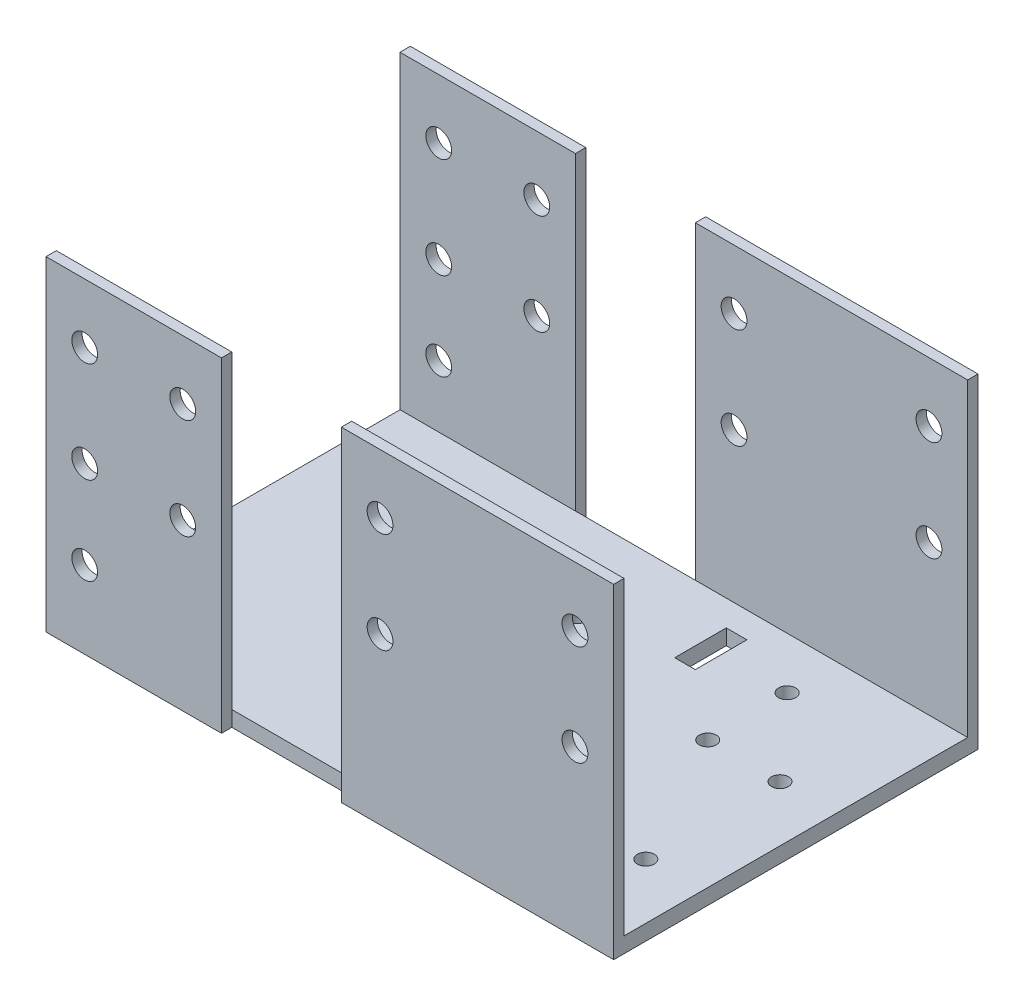
SolidWorks part; units mm, degrees
ref_plane "前视基准面" through (0, 0, 0) normal (0, 0, 1) x (1, 0, 0)
ref_plane "上视基准面" through (0, 0, 0) normal (0, 1, 0) x (1, 0, 0)
ref_plane "右视基准面" through (0, 0, 0) normal (1, 0, 0) x (0, 0, -1)
sketch "草图1" plane through (0, 0, 0) normal (0, 1, 0) x (1, 0, 0)
  line L1 (0, 0) -> (110, 0)
  line L2 (0, 0) -> (0, -66.6)
  line L3 (0, -66.6) -> (110, -66.6)
  line L4 (110, 0) -> (110, -66.6)
  line L5 (0, -66.6) -> (34, -66.6)
  line L6 (0, -66.6) -> (0, -68.6)
  line L7 (0, -68.6) -> (34, -68.6)
  line L8 (34, -66.6) -> (34, -68.6)
  line L9 (110, -66.6) -> (57.23, -66.6)
  line L10 (110, -66.6) -> (110, -68.6)
  line L11 (110, -68.6) -> (57.23, -68.6)
  line L12 (57.23, -66.6) -> (57.23, -68.6)
  line L13 (0, 0) -> (34, 0)
  line L14 (0, 0) -> (0, 2)
  line L15 (0, 2) -> (34, 2)
  line L16 (34, 0) -> (34, 2)
  line L17 (57.23, 0) -> (110, 0)
  line L18 (57.23, 0) -> (57.23, 2)
  line L19 (57.23, 2) -> (110, 2)
  line L20 (110, 0) -> (110, 2)
  line L21 (85.228, -59.5618) -> (99.228, -59.5618)
  line L22 (85.228, -59.5618) -> (85.228, -63.5618)
  line L23 (85.228, -63.5618) -> (99.228, -63.5618)
  line L24 (99.228, -59.5618) -> (99.228, -63.5618)
  line L25 (68.2195, -15) -> (72.2195, -15)
  line L26 (68.2195, -15) -> (68.2195, -5)
  line L27 (68.2195, -5) -> (72.2195, -5)
  line L28 (72.2195, -15) -> (72.2195, -5)
  line L29 (68.2195, -15) -> (72.2195, -5) construction
  line L30 (68.2195, -5) -> (72.2195, -15) construction
  circle A1 centre (99.228, -25.6) radius 1.65
  circle A2 centre (85.228, -25.6) radius 1.65
  circle A3 centre (85.228, -51.6) radius 1.65
  circle A4 centre (99.228, -51.6) radius 1.65
  circle A5 centre (85, -10) radius 1.65
  circle A6 centre (9.8926, -17.5518) radius 1.65
  circle A7 centre (51.8926, -17.5623) radius 1.65
  circle A8 centre (53.3861, -59.5623) radius 1.65
  circle A9 centre (11.3861, -59.5518) radius 1.65
  point P31 (70.2195, -10)
  point P44 (11.2794, -51.6)
  point P45 (41.2556, -56.573)
  point P46 (23.8673, -56.5746)
  point P47 (9.8926, -58.4932)
  point P48 (51.4966, -59.5618)
  point P49 (0, 0)
  point P50 (11.3861, -59.5623)
  dimension "D8" = 3.3
  dimension "D9" = 3.3
  dimension "D10" = 3.3
  dimension "D11" = 3.3
  dimension "D12" = 14
  dimension "D13" = 26
  dimension "D14" = 14
  dimension "D15" = 15
  dimension "D17" = 3.3
  dimension "D18" = 10
  dimension "D19" = 25
  dimension "D23" = 42
  dimension "D24" = 42
  dimension "D25" = 42
  dimension "D26" = 42
  dimension "D27" = 3.3
  dimension "D28" = 3.3
  dimension "D29" = 3.3
  dimension "D30" = 3.3
  dimension "D1" = 110
  dimension "D2" = 66.6
  dimension "D3" = 2
  dimension "D4" = 34
  dimension "D5" = 52.77
  dimension "D6" = 34
  dimension "D7" = 2
  dimension "D16" = 4
  dimension "D20" = 4
  dimension "D21" = 10
  dimension "D22" = 14
extrude "凸台-拉伸2" add sketch "草图1" along normal blind 3 contours L4 L1 L2 L3 region at (54.5212, 0, 33.1864)
extrude "凸台-拉伸3" add sketch "草图1<3>" along normal blind 63 contours L6 L7 L8 L5 | L10 L11 L12 L9 | L17 L18 L19 L20 | L14 L15 L16 L13
sketch "草图1<3>" plane through (0, 0, 0) normal (0, 1, 0) x (1, 0, 0) same geometry as "草图1"
sketch "草图2" plane through (0, 0, 68.6) normal (0, 0, 1) x (1, 0, 0)
  line L1 (57.23, 63) -> (57.23, 0) construction
  line L2 (110, 63) -> (110, 0) construction
  line L4 (34, 3) -> (57.23, 3) construction
  line L5 (34, 0) -> (57.23, 0) construction
  line L6 (34, 63) -> (34, 0) construction
  line L7 (0, 63) -> (0, 0) construction
  line L8 (110, 63) -> (57.23, 63) construction
  line L9 (0, 63) -> (34, 63) construction
  circle A0 centre (64.73, 32) radius 2.5
  circle A1 centre (102.5, 32) radius 2.5
  circle A2 centre (64.73, 51.5) radius 2.5
  circle A3 centre (102.5, 51.5) radius 2.5
  circle A4 centre (26.5, 32) radius 2.5
  circle A5 centre (7.5, 32) radius 2.5
  circle A6 centre (26.5, 51.5) radius 2.5
  circle A7 centre (7.5, 51.5) radius 2.5
  dimension "D2" = 7.5
  dimension "D3" = 11.5
  dimension "D4" = 7.5
  dimension "D6" = 5
  dimension "D7" = 5
  dimension "D8" = 5
  dimension "D9" = 5
  dimension "D12" = 7.5
  dimension "D13" = 5
  dimension "D14" = 5
  dimension "D15" = 5
  dimension "D16" = 5
  dimension "D17" = 11.5
  dimension "D19" = 11.5
  dimension "D20" = 11.5
  dimension "D21" = 19.5
  dimension "D22" = 19.5
  dimension "D5" = 19.5
  dimension "D10" = 3
  dimension "D11" = 7.5
  dimension "D18" = 19.5
extrude "切除-拉伸1" cut sketch "草图2" against normal through all both and the other way through all
sketch "草图4" plane through (0, 0, -2) normal (0, 0, -1) x (-1, 0, 0)
  line L0 (0, 63) -> (0, 0) construction
  line L1 (0, 0) -> (-34, 0) construction
  circle A0 centre (-7.5, 15) radius 2.5
  dimension "D1" = 5
  dimension "D2" = 7.5
  dimension "D3" = 15
extrude "切除-拉伸2" cut sketch "草图4" against normal through all both and the other way through all
